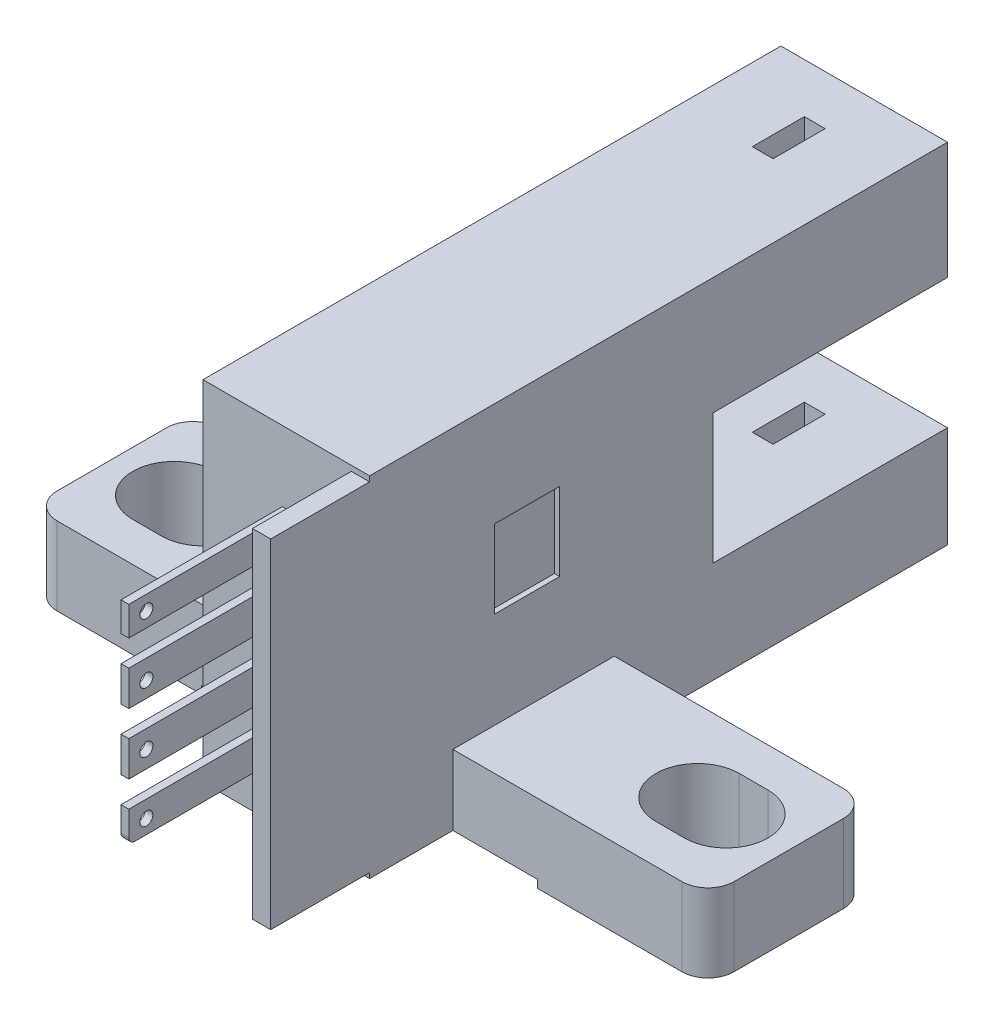
SolidWorks part; units mm, degrees
ref_plane "Front Plane" through (0, 0, 0) normal (0, 0, 1) x (1, 0, 0)
ref_plane "Top Plane" through (0, 0, 0) normal (0, 1, 0) x (1, 0, 0)
ref_plane "Right Plane" through (0, 0, 0) normal (1, 0, 0) x (0, 0, -1)
sketch "Sketch1" plane through (0, 0, 0) normal (0, 1, 0) x (1, 0, 0)
  line L0 (-24.5596, 0) -> (26.9759, 0) construction
  line L1 (0, -14.4283) -> (0, 19.6123) construction
  line L2 (-3.2, 3.1) -> (-12, 3.1)
  line L3 (12, -3.1) -> (3.2, -3.1)
  line L4 (13, -2.1) -> (13, 2.1)
  line L5 (12, 3.1) -> (3.2, 3.1)
  line L6 (-13, -2.1) -> (-13, 2.1)
  line L9 (-3.2, -6.3) -> (3.2, -6.3)
  line L10 (-3.2, -6.3) -> (-3.2, 15.9)
  line L11 (-3.2, 15.9) -> (3.2, 15.9)
  line L12 (3.2, -6.3) -> (3.2, 15.9)
  line L13 (-0.4, 12) -> (0.4, 12)
  line L14 (-0.4, 12) -> (-0.4, 14)
  line L15 (-0.4, 14) -> (0.4, 14)
  line L16 (0.4, 12) -> (0.4, 14)
  line L17 (-0.4, 12) -> (0.4, 14) construction
  line L18 (-0.4, 14) -> (0.4, 12) construction
  line L19 (-3.2, -3.1) -> (-12, -3.1)
  line L21 (-0.15, -6.3) -> (0.15, -6.3)
  line L22 (-0.15, -6.3) -> (-0.15, -10.1)
  line L23 (-0.15, -10.1) -> (0.15, -10.1)
  line L24 (0.15, -6.3) -> (0.15, -10.1)
  line L26 (10.6, 1.6) -> (9.5, 1.6)
  line L27 (-10.6, 1.6) -> (-9.5, 1.6)
  line L29 (-10.6, -1.6) -> (-9.5, -1.6)
  line L31 (10.6, -1.6) -> (9.5, -1.6)
  arc A0 (-12, 3.1) -> (-13, 2.1) centre (-12, 2.1) ccw
  arc A1 (12, 3.1) -> (13, 2.1) centre (12, 2.1) cw
  arc A2 (12, -3.1) -> (13, -2.1) centre (12, -2.1) ccw
  arc A3 (-12, -3.1) -> (-13, -2.1) centre (-12, -2.1) cw
  arc A4 (-9.5, -1.6) -> (-9.5, 1.6) centre (-9.5, 0) ccw
  arc A5 (-10.6, 1.6) -> (-10.6, -1.6) centre (-10.6, 0) ccw
  arc A6 (9.5, -1.6) -> (9.5, 1.6) centre (9.5, 0) cw
  arc A7 (10.6, 1.6) -> (10.6, -1.6) centre (10.6, 0) cw
  point P5 (0, 0)
  point P14 (9.5, 0)
  point P15 (0, 13)
  point P26 (-9.5, 0)
  dimension "D10" = 2
  dimension "D13" = 3.2
  dimension "D2" = 6.4
  dimension "D3" = 6.3
  dimension "D4" = 0.8
  dimension "D5" = 2
  dimension "D6" = 13
  dimension "D7" = 22.2
  dimension "D8" = 19
  dimension "D9" = 26
  dimension "D11" = 0.3
  dimension "D12" = 3.8
  dimension "D14" = 6.2
extrude "Boss-Extrude1" add sketch "Sketch1" along normal blind 13.7 contours L12 L11 L10 L9 | L14 L15 L16 L13
extrude "Boss-Extrude2" add sketch "Sketch1<4>" along normal blind 3 contours L3 A2 L4 A1 L5 L12 L26 A7 L31 A6 | A3 L19 L10 L2 A0 L6 A5 L27 A4 L29 region at (-7.5965, 0, 0) region at (7.5965, 0, 0)
sketch "Sketch1<4>" plane through (0, 0, 0) normal (0, 1, 0) x (1, 0, 0) same geometry as "Sketch1"
sketch "Sketch2" plane through (3.2, 0, 0) normal (1, 0, 0) x (0, 0, -1)
  line L0 (-9.6152, 6.7) -> (19.0707, 6.7) construction
  line L1 (15.9, 13.7) -> (15.9, 0) construction
  line L2 (15.9, 9.2) -> (6.9, 9.2)
  line L3 (15.9, 9.2) -> (15.9, 4.2)
  line L4 (15.9, 4.2) -> (6.9, 4.2)
  line L5 (6.9, 9.2) -> (6.9, 4.2)
  line L7 (-1.5, 6.7) -> (1, 6.7)
  line L8 (-1.5, 6.7) -> (-1.5, 9.7)
  line L9 (-1.5, 9.7) -> (1, 9.7)
  line L10 (1, 6.7) -> (1, 9.7)
  line M13 (15.9, 0) -> (15.9, 13.7)
  dimension "D1" = 5
  dimension "D2" = 9
  dimension "D3" = 8.4
  dimension "D4" = 2.5
  dimension "D5" = 3
extrude "Cut-Extrude1" cut sketch "Sketch2" against normal through all contours L5 L0 L3 L2 | L0 L5 L4 M13 region at (3.2, 7.95, -11.4) region at (3.2, 5.45, -11.4)
extrude "Cut-Extrude2" cut sketch "Sketch2<3>" against normal blind 0.2 contours L7 L10 L9 L8 region at (3.2, 8.2, 0.25)
sketch "Sketch2<3>" plane through (3.2, 0, 0) normal (1, 0, 0) x (0, 0, -1) same geometry as "Sketch2"
sketch "Sketch3" plane through (0, 0, 0) normal (0, -1, 0) x (1, 0, 0)
  line L0 (-3.2, 3.1) -> (-12, 3.1) construction
  line L1 (-6.45, 3.1) -> (-3.2, 3.1)
  line L2 (-6.45, 3.1) -> (-6.45, -3.1)
  line L3 (-6.45, -3.1) -> (-3.2, -3.1)
  line L4 (6.45, 3.1) -> (6.45, -3.1)
  line L5 (12, -3.1) -> (3.2, -3.1) construction
  line L6 (3.2, 3.1) -> (6.45, 3.1)
  line L7 (-3.2, 6.3) -> (3.2, 6.3)
  line L8 (-3.2, 6.3) -> (-3.2, 3.1)
  line L9 (-3.2, -15.9) -> (3.2, -15.9)
  line L10 (3.2, 6.3) -> (3.2, 3.1)
  line L11 (3.2, -3.1) -> (3.2, -15.9)
  line L12 (3.2, -3.1) -> (6.45, -3.1)
  line L13 (-3.2, -3.1) -> (-3.2, -15.9)
  line L14 (0, 10.3176) -> (0, -26.4381) construction
  dimension "D1" = 12.9
extrude "Cut-Extrude3" cut sketch "Sketch3" against normal blind 0.3
ref_plane "Plane4" through (0, 7, 0) normal (0, 1, 0) x (1, 0, 0)
sketch "Sketch4" plane through (0, 7, 0) normal (0, 1, 0) x (1, 0, 0)
  line L0 (0, -4.5243) -> (0, -9.2106) construction
  line L1 (-3.2, -6.3) -> (3.2, -6.3) construction
  line L2 (-0.15, -6.3) -> (0.15, -6.3)
  line L3 (-0.15, -6.3) -> (-0.15, -12.5)
  line L4 (-0.15, -12.5) -> (0.15, -12.5)
  line L5 (0.15, -6.3) -> (0.15, -12.5)
  line L7 (2.5, -6.3) -> (3.2, -6.3)
  line L8 (2.5, -6.3) -> (2.5, -10.1)
  line L9 (2.5, -10.1) -> (3.2, -10.1)
  line L10 (3.2, -6.3) -> (3.2, -10.1)
  line L11 (3.2, -6.3) -> (3.2, 15.9) construction
  dimension "D1" = 0.7
  dimension "D2" = 0.3
  dimension "D3" = 6.2
  dimension "D4" = 3.8
extrude "Boss-Extrude3" add sketch "Sketch4" along normal blind 6.5 and the other way blind 6.5 contours L10 L7 L8 L9 region at (2.85, 7, 8.2)
extrude "Boss-Extrude4" add sketch "Sketch4<3>" along normal blind 4 and the other way blind 4 contours L3 L4 L5 L2
sketch "Sketch4<3>" plane through (0, 7, 0) normal (0, 1, 0) x (1, 0, 0) same geometry as "Sketch4"
sketch "Sketch7" plane through (-0.15, 0, 0) normal (-1, 0, 0) x (0, 0, 1)
  line L0 (3.1808, 7) -> (13.3599, 7) construction
  line L1 (12.2608, 3) -> (12.5, 3)
  line L6 (12.5, 3) -> (12.5, 3.2392)
  line L15 (12.5, 3) -> (12.5, 11) construction
  line L20 (6.3, 3) -> (6.3, 11) construction
  line L21 (6.3, 3) -> (12.5, 3) construction
  line L22 (12.5, 6.5311) -> (6.3, 6.5311)
  line L23 (12.5, 6.5311) -> (12.5, 7.5311)
  line L24 (12.5, 7.5311) -> (6.3, 7.5311)
  line L25 (6.3, 6.5311) -> (6.3, 7.5311)
  line L26 (6.3, 8.8762) -> (12.5, 8.8762)
  line L27 (6.3, 8.8762) -> (6.3, 9.8762)
  line L28 (6.3, 9.8762) -> (12.5, 9.8762)
  line L29 (12.5, 8.8762) -> (12.5, 9.8762)
  line L30 (6.3, 4.1851) -> (12.5, 4.1851)
  line L31 (6.3, 4.1851) -> (6.3, 5.1851)
  line L32 (6.3, 5.1851) -> (12.5, 5.1851)
  line L33 (12.5, 4.1851) -> (12.5, 5.1851)
  circle A0 centre (11.8246, 3.5387) radius 0.25
  circle A1 centre (11.8246, 5.8387) radius 0.25
  circle A2 centre (11.8246, 8.1387) radius 0.25
  circle A3 centre (11.8246, 10.4387) radius 0.25
  arc A4 (12.2608, 3) -> (12.5, 3.2392) centre (12.2608, 3.2392) ccw
  dimension "D4" = 0.5
  dimension "D1" = 1
  dimension "D2" = 1
  dimension "D3" = 1
  dimension "D5" = 4
extrude "Cut-Extrude4" cut sketch "Sketch7" against normal blind 1
